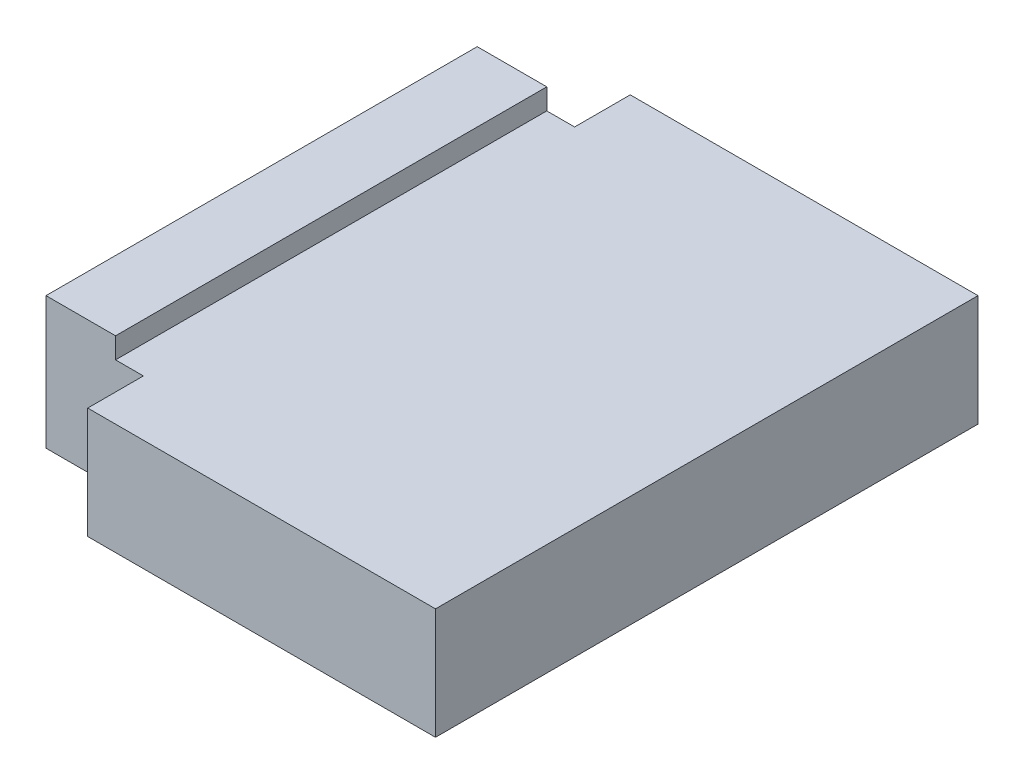
SolidWorks part; units mm, degrees
ref_plane "前视基准面" through (0, 0, 0) normal (0, 0, 1) x (1, 0, 0)
ref_plane "上视基准面" through (0, 0, 0) normal (0, 1, 0) x (1, 0, 0)
ref_plane "右视基准面" through (0, 0, 0) normal (1, 0, 0) x (0, 0, -1)
sketch "草图2" plane through (0, 0, 0) normal (0, 1, 0) x (1, 0, 0)
  line L0 (-18, 39) -> (-18, 31)
  line L1 (32, -39) -> (-18, -39)
  line L2 (32, -39) -> (32, 39)
  line L3 (32, 39) -> (-18, 39)
  line L4 (-32, -31) -> (-32, 31)
  line L5 (32, -39) -> (-32, 39) construction
  line L6 (32, 39) -> (-32, -39) construction
  line L7 (-18, 31) -> (-32, 31)
  line L8 (-32, 31) -> (-18, 31)
  line L9 (-18, -39) -> (-18, -31)
  line L10 (-18, -31) -> (-32, -31)
  point P0 (0, 0)
  dimension "D1" = 64
  dimension "D2" = 78
  dimension "D3" = 8
  dimension "D4" = 14
  dimension "D5" = 8
extrude "凸台-拉伸2" add sketch "草图2" along normal blind 16 contours L10 L9 L1 L2 L3 L0 L7 L4 region at (1.1745, 0, 0)
sketch "草图5" plane through (0, 16, 0) normal (0, 1, 0) x (1, 0, 0)
  line L0 (-18, -31) -> (-32, -31) construction
  line L1 (-32, 31) -> (-22, 31)
  line L2 (-32, 31) -> (-32, -31)
  line L3 (-32, -31) -> (-22, -31)
  line L4 (-22, 31) -> (-22, -31)
  dimension "D1" = 10
extrude "凸台-拉伸3" add sketch "草图5" along normal blind 3
